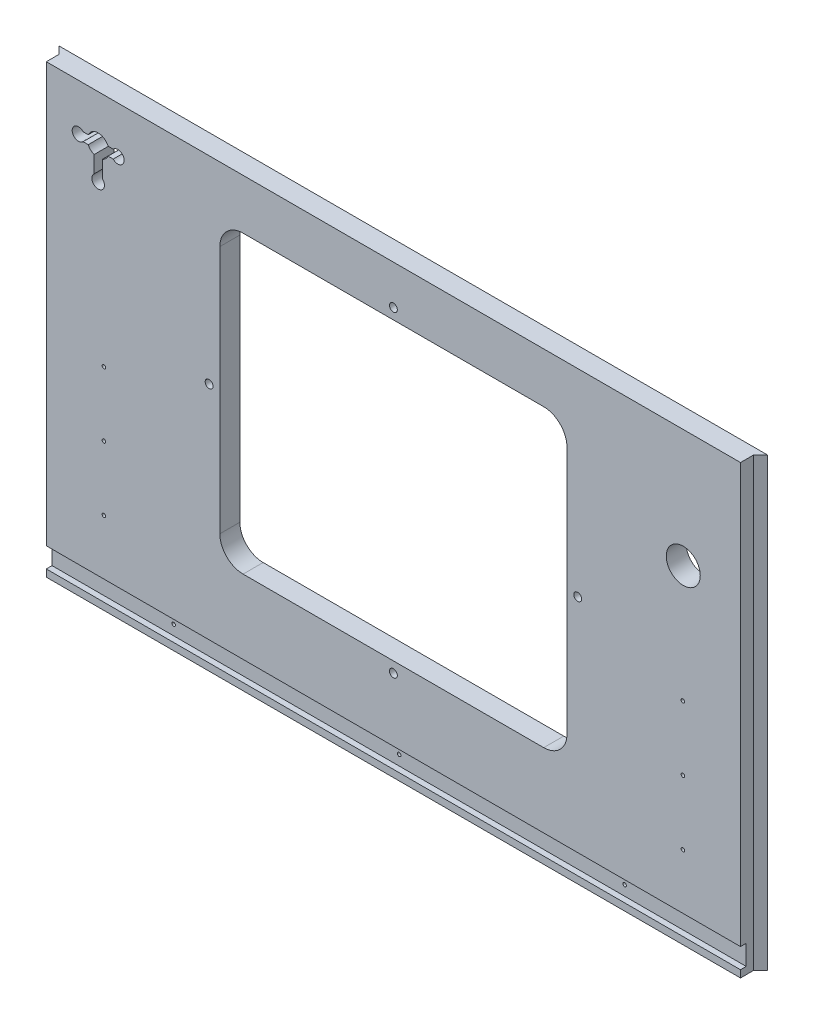
SolidWorks part; units mm, degrees
material "Maple"
ref_plane "Front Plane" through (0, 0, 0) normal (0, 0, 1) x (1, 0, 0)
ref_plane "Top Plane" through (0, 0, 0) normal (0, 1, 0) x (1, 0, 0)
ref_plane "Right Plane" through (0, 0, 0) normal (1, 0, 0) x (0, 0, -1)
sketch "Sketch1" plane through (0, 0, 0) normal (0, 0, 1) x (1, 0, 0)
  line L0 (8932.6508, -5243.5125) -> (10226.1458, -5243.5125)
  line L1 (9086.3208, -4722.0918) -> (10222.9708, -4853.7812)
  line L2 (8914.8708, -6342.0625) -> (10197.5708, -6342.0625)
  line L3 (8914.8708, -5808.6625) -> (10197.5708, -5808.6625)
  line L4 (8919.6333, -5253.0375) -> (10218.2083, -5253.0375)
  line L5 (9134.2633, -4656.1375) -> (9134.2633, -4638.3575)
  line L6 (9091.0833, -4638.3575) -> (9134.2633, -4638.3575)
  line L7 (9091.0833, -4567.2375) -> (9091.0833, -4638.3575)
  line L8 (9134.2633, -4656.1375) -> (9581.3033, -4656.1375)
  line L9 (9091.0833, -4567.2375) -> (9624.4833, -4567.2375)
  line L10 (9581.3033, -4656.1375) -> (9581.3033, -4638.3575)
  line L11 (9581.3033, -4638.3575) -> (9624.4833, -4638.3575)
  line L12 (9624.4833, -4567.2375) -> (9624.4833, -4638.3575)
  line L13 (8932.6508, -5225.7325) -> (9344.9775, -5225.7325)
  line L14 (8932.6508, -5256.2125) -> (8932.6508, -5243.5125)
  line L15 (8911.6958, -5256.2125) -> (8932.6508, -5256.2125)
  line L16 (8914.8708, -4722.0918) -> (9086.3208, -4722.0918)
  line L17 (8911.6958, -4715.5913) -> (8932.6508, -4715.5913)
  line L18 (8914.8708, -6342.0625) -> (8914.8708, -5808.6625)
  line L19 (12082.9917, -4722.0918) -> (10946.3417, -4853.7812)
  line L20 (12236.6617, -5243.5125) -> (10943.1667, -5243.5125)
  line L21 (10951.1042, -5253.0375) -> (12249.6792, -5253.0375)
  line L22 (10838.3917, -5656.2625) -> (11308.2917, -5656.2625)
  line L23 (10838.3917, -5719.7625) -> (11308.2917, -5719.7625)
  line L24 (10838.3917, -5742.5368) -> (11308.2917, -5742.5368)
  line L25 (10806.6417, -6342.0625) -> (11340.0417, -6342.0625)
  line L26 (10803.4667, -6335.7125) -> (11343.2167, -6335.7125)
  line L27 (10803.4667, -6317.9325) -> (11343.2167, -6317.9325)
  line L28 (10943.1667, -5225.7325) -> (11376.4483, -5225.7325)
  line L29 (11506.7292, -4754.5625) -> (10806.6417, -4827.5875)
  line L30 (11506.7292, -4567.2375) -> (11506.7292, -4754.5625)
  line L31 (10806.6417, -4567.2375) -> (10806.6417, -4827.5875)
  line L32 (10806.6417, -4567.2375) -> (11506.7292, -4567.2375)
  line L33 (10235.6708, -6329.3625) -> (10245.1958, -6329.3625)
  line L34 (10245.1958, -6329.3625) -> (10254.7208, -6278.5625)
  line L35 (10302.3458, -6329.3625) -> (10311.8708, -6278.5625)
  line L36 (10302.3458, -6329.3625) -> (10292.8208, -6329.3625)
  line L37 (10245.1958, -5821.3625) -> (10254.7208, -5872.1625)
  line L38 (10235.6708, -5821.3625) -> (10245.1958, -5821.3625)
  line L39 (10292.8208, -5821.3625) -> (10302.3458, -5821.3625)
  line L40 (10302.3458, -5821.3625) -> (10311.8708, -5872.1625)
  line L41 (10235.6708, -5821.3625) -> (10235.6708, -6329.3625)
  line L42 (10254.7208, -5872.1625) -> (10254.7208, -6278.5625)
  line L43 (10311.8708, -5872.1625) -> (10311.8708, -6278.5625)
  line L44 (10292.8208, -5821.3625) -> (10292.8208, -6329.3625)
  line L45 (8932.6508, -5225.7325) -> (8932.6508, -4715.5913)
  line L46 (8911.6958, -4715.5913) -> (8911.6958, -5256.2125)
  line L47 (8914.8708, -5248.275) -> (8914.8708, -4722.0918)
  line L48 (8919.6333, -5253.0375) -> (8914.8708, -5248.275)
  line L49 (8914.8708, -5145.0875) -> (8937.426, -5145.0875)
  line L50 (8914.8708, -5202.2375) -> (8937.426, -5202.2375)
  line L51 (10838.3917, -5656.2625) -> (10838.3917, -5719.7625)
  line L52 (10832.0417, -5736.1868) -> (10856.1717, -5736.1868)
  line L53 (10806.6417, -6342.0625) -> (10806.6417, -5818.7368)
  line L54 (10832.0417, -5649.9125) -> (10856.1717, -5649.9125)
  line L55 (10832.0417, -5726.1125) -> (10856.1717, -5726.1125)
  line L56 (10806.6417, -5818.7368) -> (10833.9015, -5818.7368)
  line L57 (10832.0417, -5806.0442) -> (10851.6815, -5806.0442)
  line L58 (10856.1717, -5801.5541) -> (10856.1717, -5736.1868)
  line L59 (10838.3917, -5814.2467) -> (10838.3917, -5742.5368)
  line L60 (10832.0417, -5806.0442) -> (10832.0417, -5736.1868)
  line L61 (10803.4667, -6317.9325) -> (10803.4667, -6335.7125)
  line L62 (10197.5708, -5808.6625) -> (10197.5708, -6342.0625)
  line L63 (9762.3842, -6348.4125) -> (9762.3842, -5802.3125)
  line L64 (9780.1642, -6348.4125) -> (9762.3842, -6348.4125)
  line L65 (9780.1642, -5802.3125) -> (9780.1642, -6348.4125)
  line L66 (9762.3842, -5802.3125) -> (9780.1642, -5802.3125)
  line L67 (9332.2775, -6348.4125) -> (9332.2775, -5802.3125)
  line L68 (9332.2775, -6348.4125) -> (9350.0575, -6348.4125)
  line L69 (9350.0575, -5802.3125) -> (9350.0575, -6348.4125)
  line L70 (9332.2775, -5802.3125) -> (9350.0575, -5802.3125)
  line L71 (9993.8374, -6061.075) -> (9993.8374, -6045.2418)
  line L72 (9998.5999, -6065.8375) -> (10014.4331, -6065.8375)
  line L73 (9998.5999, -6084.8875) -> (10014.4331, -6084.8875)
  line L74 (9993.8374, -6105.4832) -> (9993.8374, -6089.65)
  line L75 (9974.7874, -6105.4832) -> (9974.7874, -6089.65)
  line L76 (9954.1917, -6084.8875) -> (9970.0249, -6084.8875)
  line L77 (9974.7874, -6061.075) -> (9974.7874, -6045.2418)
  line L78 (9954.1917, -6065.8375) -> (9970.0249, -6065.8375)
  line L79 (10793.9417, -6237.2875) -> (10816.4969, -6237.2875)
  line L80 (10793.9417, -6294.4375) -> (10816.4969, -6294.4375)
  line L81 (10856.1717, -5649.9125) -> (10856.1717, -5726.1125)
  line L82 (10832.0417, -5726.1125) -> (10832.0417, -5649.9125)
  line L83 (10226.1458, -5225.7325) -> (10226.1458, -5243.5125)
  line L84 (10205.1908, -5257.8) -> (10205.1908, -4844.2499)
  line L85 (10230.9083, -4844.2499) -> (10230.9083, -5257.8)
  line L86 (10205.1908, -5257.8) -> (10230.9083, -5257.8)
  line L87 (10205.1908, -4844.2499) -> (10230.9083, -4844.2499)
  line L88 (10946.3417, -5176.8375) -> (10968.8969, -5176.8375)
  line L89 (9349.4676, -5141.9125) -> (9358.2674, -5141.9125)
  line L90 (10946.3417, -5119.6875) -> (10968.8969, -5119.6875)
  line L91 (9929.011, -4660.9635) -> (10066.0807, -4660.9635)
  line L92 (9929.011, -4678.7435) -> (10066.0807, -4678.7435)
  line L93 (10943.1667, -5225.7325) -> (10943.1667, -5243.5125)
  line L94 (10946.3417, -5248.275) -> (10951.1042, -5253.0375)
  line L95 (10946.3417, -5257.8063) -> (10946.3417, -4849.0188)
  line L96 (10964.1217, -5257.8) -> (10964.1217, -4844.2499)
  line L97 (10938.4042, -4844.2499) -> (10938.4042, -5257.8)
  line L98 (10938.4042, -5257.8) -> (10964.1217, -5257.8)
  line L99 (10964.1217, -4844.2499) -> (10938.4042, -4844.2499)
  line L100 (10344.8908, -4560.8875) -> (10369.0208, -4560.8875)
  line L101 (10344.8908, -4560.8875) -> (10369.0208, -4560.8875)
  line L102 (10800.2917, -4560.8875) -> (10824.4217, -4560.8875)
  line L103 (10200.4156, -5119.6875) -> (10222.9708, -5119.6875)
  line L104 (10200.4156, -5176.8375) -> (10222.9708, -5176.8375)
  line L105 (9344.9775, -5146.4026) -> (9344.9775, -5225.7325)
  line L106 (10344.8908, -4560.8875) -> (10344.8908, -4833.9375)
  line L107 (9792.8642, -5225.7325) -> (9792.8642, -5146.4026)
  line L108 (9362.7575, -5225.7325) -> (9775.0842, -5225.7325)
  line L109 (9680.3633, -4761.8396) -> (9680.3633, -4559.9604)
  line L110 (9656.2333, -4559.9604) -> (9680.3633, -4559.9604)
  line L111 (9656.2333, -4761.8396) -> (9680.3633, -4761.8396)
  line L112 (9656.2333, -4761.8396) -> (9656.2333, -4559.9604)
  line L113 (9779.5743, -5141.9125) -> (9788.374, -5141.9125)
  line L114 (10070.5708, -4665.4536) -> (10070.5708, -4674.2534)
  line L115 (9924.5208, -4674.2534) -> (9924.5208, -4665.4536)
  line L116 (12127.4417, -6188.3925) -> (12205.5015, -6188.3925)
  line L117 (12209.9917, -6170.6125) -> (12209.9917, -6183.9024)
  line L118 (9792.8642, -5225.7325) -> (10226.1458, -5225.7325)
  line L119 (9662.5833, -4754.5625) -> (10362.6708, -4827.5875)
  line L120 (9662.5833, -4567.2375) -> (9662.5833, -4754.5625)
  line L121 (10362.6708, -4567.2375) -> (10362.6708, -4827.5875)
  line L122 (9662.5833, -4567.2375) -> (10362.6708, -4567.2375)
  line L123 (10824.4217, -4833.9375) -> (10800.2917, -4833.9375)
  line L124 (10800.2917, -4833.9375) -> (10800.2917, -4560.8875)
  line L125 (10824.4217, -4560.8875) -> (10824.4217, -4833.9375)
  line L126 (10344.8908, -4833.9375) -> (10369.0208, -4833.9375)
  line L127 (10369.0208, -4833.9375) -> (10369.0208, -4560.8875)
  line L128 (10222.9708, -5248.275) -> (10218.2083, -5253.0375)
  line L129 (10222.9708, -5257.8063) -> (10222.9708, -4849.0188)
  line L130 (11734.6544, -5701.375) -> (11739.2301, -5701.375)
  line L131 (9362.7575, -5225.7325) -> (9362.7575, -5146.4026)
  line L132 (9775.0842, -5146.4026) -> (9775.0842, -5225.7325)
  line L133 (11761.3864, -5701.375) -> (11756.8282, -5701.375)
  line L134 (11734.6544, -5693.755) -> (11739.2301, -5693.755)
  line L135 (11761.4039, -5693.755) -> (11756.8282, -5693.755)
  line L136 (11734.6544, -5701.375) -> (11739.2301, -5701.375)
  line L137 (11744.3462, -5721.3024) -> (11744.3462, -5706.4179)
  line L138 (11751.7122, -5721.3024) -> (11751.7122, -5706.4179)
  line L139 (11740.0917, -6170.6125) -> (11740.0917, -6183.9024)
  line L140 (11689.2917, -6188.3925) -> (11822.6417, -6188.3925)
  line L141 (11689.2917, -6348.4093) -> (11689.2917, -6164.2657)
  line L142 (11689.2917, -6164.2657) -> (11746.4417, -6164.2657)
  line L143 (11746.4417, -6164.2657) -> (11746.4417, -6188.3925)
  line L144 (11689.2917, -6164.2657) -> (11746.4417, -6164.2657)
  line L145 (11340.0417, -5818.7368) -> (11340.0417, -6342.0625)
  line L146 (11290.5117, -5726.1125) -> (11314.6417, -5726.1125)
  line L147 (11290.5117, -5649.9125) -> (11290.5117, -5726.1125)
  line L148 (11340.0417, -5818.7368) -> (11312.7818, -5818.7368)
  line L149 (11314.6417, -5806.0442) -> (11295.0018, -5806.0442)
  line L150 (11290.5117, -5801.5541) -> (11290.5117, -5736.1868)
  line L151 (11308.2917, -5814.2467) -> (11308.2917, -5742.5368)
  line L152 (11314.6417, -5806.0442) -> (11314.6417, -5736.1868)
  line L153 (11290.5117, -5736.1868) -> (11314.6417, -5736.1868)
  line L154 (11848.0417, -6267.1325) -> (11962.3417, -6267.1325)
  line L155 (11962.3417, -6267.1325) -> (11962.3417, -6203.6325)
  line L156 (11343.2167, -6317.9325) -> (11343.2167, -6335.7125)
  line L157 (11365.4417, -5656.2625) -> (11365.4417, -5719.7625)
  line L158 (11365.4417, -5656.2625) -> (11479.7417, -5656.2625)
  line L159 (11778.1917, -6071.3937) -> (11802.3217, -6071.3937)
  line L160 (11314.6417, -5726.1125) -> (11314.6417, -5649.9125)
  line L161 (11314.6417, -5649.9125) -> (11290.5117, -5649.9125)
  line L162 (11308.2917, -5719.7625) -> (11308.2917, -5656.2625)
  line L163 (11689.2917, -6348.4093) -> (11713.4217, -6348.4093)
  line L164 (12203.6417, -6164.2657) -> (12260.7917, -6164.2657)
  line L165 (11713.4217, -6348.4093) -> (11713.4217, -6164.2657)
  line L166 (11695.6417, -6342.0625) -> (11695.6417, -6170.6125)
  line L167 (11695.6417, -6048.5337) -> (11699.4517, -6052.3437)
  line L168 (11822.6417, -6292.5325) -> (11822.6417, -6188.3925)
  line L169 (11695.6417, -6342.0625) -> (11695.6417, -6170.6125)
  line L170 (11848.0417, -6203.6325) -> (11962.3417, -6203.6325)
  line L171 (11848.0417, -6203.6325) -> (11848.0417, -6267.1325)
  line L172 (11987.7417, -6267.1325) -> (11987.7417, -6203.6325)
  line L173 (11784.5417, -6077.7437) -> (11784.5417, -6141.2438)
  line L174 (11517.8417, -5656.2625) -> (11632.1417, -5656.2625)
  line L175 (11632.1417, -5656.2625) -> (11632.1417, -5719.7625)
  line L176 (11632.1417, -5719.7625) -> (11517.8417, -5719.7625)
  line L177 (11517.8417, -5719.7625) -> (11517.8417, -5656.2625)
  line L178 (11692.4667, -6028.2137) -> (11692.4667, -6045.9937)
  line L179 (11695.6417, -5979.3188) -> (11718.1969, -5979.3188)
  line L180 (11695.6417, -5922.1687) -> (11718.1969, -5922.1687)
  line L181 (11821.0415, -5722.9375) -> (11821.0415, -5943.6)
  line L182 (11687.7042, -5651.5) -> (11701.9917, -5651.5)
  line L183 (11687.7042, -5651.5) -> (11687.7042, -6055.5251)
  line L184 (11687.7042, -6055.5251) -> (11701.9917, -6055.5251)
  line L185 (11701.9917, -6055.5251) -> (11701.9917, -5651.5)
  line L186 (11695.6417, -6055.2013) -> (11695.6417, -5649.595)
  line L187 (11695.6417, -5656.2625) -> (11695.6417, -6048.5337)
  line L188 (11695.6417, -6170.6125) -> (11740.0917, -6170.6125)
  line L189 (12203.6417, -6164.2657) -> (12203.6417, -6188.3925)
  line L190 (12254.4417, -6342.0625) -> (12254.4417, -6170.6125)
  line L191 (12129.0419, -5943.6) -> (12129.0419, -5722.9375)
  line L192 (12254.4417, -6048.5337) -> (12250.6317, -6052.3437)
  line L193 (12257.6167, -6045.9937) -> (12257.6167, -6028.2137)
  line L194 (12248.0917, -5651.5) -> (12262.3792, -5651.5)
  line L195 (12262.3792, -5651.5) -> (12262.3792, -6055.5251)
  line L196 (12262.3792, -6055.5251) -> (12248.0917, -6055.5251)
  line L197 (12248.0917, -6055.5251) -> (12248.0917, -5651.5)
  line L198 (12254.4417, -6141.2438) -> (12254.4417, -6077.7437)
  line L199 (12236.6617, -6164.2657) -> (12260.7917, -6164.2657)
  line L200 (12102.0417, -6267.1325) -> (11987.7417, -6267.1325)
  line L201 (11330.1865, -6237.2875) -> (11352.7417, -6237.2875)
  line L202 (11330.1865, -6294.4375) -> (11352.7417, -6294.4375)
  line L203 (11474.6617, -5851.8425) -> (11492.4417, -5851.8425)
  line L204 (11474.6617, -5808.6625) -> (11474.6617, -5851.8425)
  line L205 (11403.5417, -5808.6625) -> (11474.6617, -5808.6625)
  line L206 (11492.4417, -5851.8425) -> (11492.4417, -6298.8825)
  line L207 (11403.5417, -6342.0625) -> (11403.5417, -5808.6625)
  line L208 (11474.6617, -6298.8825) -> (11492.4417, -6298.8825)
  line L209 (11474.6617, -6342.0625) -> (11474.6617, -6298.8825)
  line L210 (11403.5417, -6342.0625) -> (11474.6617, -6342.0625)
  line L211 (11619.4417, -5851.8425) -> (11601.6617, -5851.8425)
  line L212 (11601.6617, -5808.6625) -> (11601.6617, -5851.8425)
  line L213 (11530.5417, -5808.6625) -> (11601.6617, -5808.6625)
  line L214 (11619.4417, -5851.8425) -> (11619.4417, -6298.8825)
  line L215 (11530.5417, -6342.0625) -> (11530.5417, -5808.6625)
  line L216 (11619.4417, -6298.8825) -> (11601.6617, -6298.8825)
  line L217 (11601.6617, -6342.0625) -> (11601.6617, -6298.8825)
  line L218 (11530.5417, -6342.0625) -> (11601.6617, -6342.0625)
  line L219 (11479.7417, -5719.7625) -> (11479.7417, -5656.2625)
  line L220 (11365.4417, -5719.7625) -> (11479.7417, -5719.7625)
  line L221 (11778.1917, -6147.5937) -> (11802.3217, -6147.5937)
  line L222 (11802.3217, -6071.3937) -> (11802.3217, -6147.5937)
  line L223 (11778.1917, -6147.5937) -> (11778.1917, -6071.3937)
  line L224 (12254.4417, -5922.1687) -> (12231.8865, -5922.1687)
  line L225 (12254.4417, -5979.3188) -> (12231.8865, -5979.3188)
  line L226 (12254.4417, -6055.2013) -> (12254.4417, -5649.595)
  line L227 (12254.4417, -6048.5337) -> (12254.4417, -5656.2625)
  line L228 (11841.6917, -5702.2873) -> (12108.3917, -5702.2873)
  line L229 (11822.6417, -6292.5325) -> (12127.4417, -6292.5325)
  line L230 (12127.4417, -6292.5325) -> (12127.4417, -6188.3925)
  line L231 (12254.4417, -6170.6125) -> (12209.9917, -6170.6125)
  line L232 (11695.6417, -6342.0625) -> (12254.4417, -6342.0625)
  line L233 (12236.6617, -6348.4093) -> (12260.7917, -6348.4093)
  line L234 (12260.7917, -6348.4093) -> (12260.7917, -6164.2657)
  line L235 (12236.6617, -6348.4093) -> (12236.6617, -6164.2657)
  line L236 (12102.0417, -6203.6325) -> (12102.0417, -6267.1325)
  line L237 (11987.7417, -6203.6325) -> (12102.0417, -6203.6325)
  line L238 (12236.6617, -6147.5937) -> (12236.6617, -6071.3937)
  line L239 (12203.6417, -6188.3925) -> (12260.7917, -6188.3925)
  line L240 (11098.7417, -4665.4536) -> (11098.7417, -4674.2534)
  line L241 (11394.2283, -5146.4026) -> (11394.2283, -5225.7325)
  line L242 (11376.4483, -5225.7325) -> (11376.4483, -5146.4026)
  line L243 (11394.2283, -5225.7325) -> (11806.555, -5225.7325)
  line L244 (11841.6917, -5964.2502) -> (12108.3917, -5964.2502)
  line L245 (12236.6617, -6147.5937) -> (12260.7917, -6147.5937)
  line L246 (12236.6617, -5256.2125) -> (12236.6617, -5243.5125)
  line L247 (12260.7917, -6147.5937) -> (12260.7917, -6071.3937)
  line L248 (12260.7917, -6071.3937) -> (12236.6617, -6071.3937)
  line L249 (12254.4417, -6077.7437) -> (11784.5417, -6077.7437)
  line L250 (11784.5417, -6141.2438) -> (12254.4417, -6141.2438)
  line L252 (12254.4417, -5656.2625) -> (11695.6417, -5656.2625)
  line L253 (11699.4517, -6052.3437) -> (12250.6317, -6052.3437)
  line L254 (11692.4667, -6045.9937) -> (12257.6167, -6045.9937)
  line L255 (11692.4667, -6028.2137) -> (12257.6167, -6028.2137)
  line L256 (11824.335, -5146.4026) -> (11824.335, -5225.7325)
  line L257 (11811.0451, -5141.9125) -> (11819.8449, -5141.9125)
  line L258 (11244.7917, -4674.2534) -> (11244.7917, -4665.4536)
  line L259 (11806.555, -5225.7325) -> (11806.555, -5146.4026)
  line L260 (11488.9492, -4761.8396) -> (11488.9492, -4559.9604)
  line L261 (11488.9492, -4559.9604) -> (11513.0792, -4559.9604)
  line L262 (11488.9492, -4761.8396) -> (11513.0792, -4761.8396)
  line L263 (11513.0792, -4761.8396) -> (11513.0792, -4559.9604)
  line L264 (11240.3015, -4660.9635) -> (11103.2318, -4660.9635)
  line L265 (11103.2318, -4678.7435) -> (11240.3015, -4678.7435)
  line L266 (12236.6617, -5225.7325) -> (12236.6617, -4715.5913)
  line L267 (12257.6167, -4715.5913) -> (12257.6167, -5256.2125)
  line L268 (12254.4417, -5248.275) -> (12254.4417, -4722.0918)
  line L269 (12236.6617, -5225.7325) -> (11824.335, -5225.7325)
  line L270 (12035.0492, -4656.1375) -> (12035.0492, -4638.3575)
  line L271 (12078.2292, -4638.3575) -> (12035.0492, -4638.3575)
  line L272 (12078.2292, -4567.2375) -> (12078.2292, -4638.3575)
  line L273 (12035.0492, -4656.1375) -> (11588.0092, -4656.1375)
  line L274 (11544.8292, -4567.2375) -> (12078.2292, -4567.2375)
  line L275 (11588.0092, -4656.1375) -> (11588.0092, -4638.3575)
  line L276 (11544.8292, -4638.3575) -> (11588.0092, -4638.3575)
  line L277 (11544.8292, -4567.2375) -> (11544.8292, -4638.3575)
  line L278 (12249.6792, -5253.0375) -> (12254.4417, -5248.275)
  line L280 (12257.6167, -5256.2125) -> (12236.6617, -5256.2125)
  line L281 (12231.8865, -5145.0875) -> (12254.4417, -5145.0875)
  line L282 (12231.8865, -5202.2375) -> (12254.4417, -5202.2375)
  line L283 (12236.6617, -4715.5913) -> (12257.6167, -4715.5913)
  line L284 (12082.9917, -4722.0918) -> (12254.4417, -4722.0918)
  line L285 (11380.9385, -5141.9125) -> (11389.7382, -5141.9125)
  circle A0 centre (8923.7608, -4778.9042) radius 1.5875
  circle A1 centre (9062.6598, -4736.3765) radius 2.3685
  circle A2 centre (9051.3958, -6281.7375) radius 22.225
  circle A3 centre (9083.1458, -6249.9875) radius 1.5875
  circle A4 centre (9083.1458, -6313.4875) radius 1.5875
  circle A5 centre (9019.6458, -6249.9875) radius 1.5875
  circle A6 centre (9019.6458, -6313.4875) radius 1.5875
  circle A7 centre (8972.3383, -5202.2375) radius 1.5875
  circle A8 centre (8923.7608, -5015.9708) radius 1.5875
  circle A9 centre (8923.7608, -5134.5042) radius 1.5875
  circle A10 centre (9054.5708, -5234.6225) radius 1.5875
  circle A11 centre (8923.7608, -4897.4375) radius 1.5875
  circle A12 centre (8972.3383, -5087.9375) radius 1.5875
  circle A13 centre (8972.3383, -5145.0875) radius 1.5875
  circle A14 centre (10847.2817, -5668.9625) radius 1.5875
  circle A15 centre (10847.2817, -5707.0625) radius 1.5875
  circle A16 centre (10847.2817, -5755.2368) radius 1.5875
  circle A17 centre (10851.4092, -6237.2875) radius 1.5875
  circle A18 centre (10851.4092, -6294.4375) radius 1.5875
  circle A19 centre (10847.2817, -5793.3442) radius 1.5875
  arc A20 (10833.9015, -5818.7368) -> (10838.3917, -5814.2467) centre (10836.1466, -5816.4918) ccw
  arc A21 (10851.6815, -5806.0442) -> (10856.1717, -5801.5541) centre (10853.9266, -5803.7992) ccw
  circle A22 centre (10882.8417, -6040.4375) radius 1.5875
  circle A23 centre (10882.8417, -6218.2375) radius 1.5875
  circle A24 centre (10882.8417, -5862.6375) radius 1.5875
  circle A25 centre (10908.2417, -6326.8225) radius 1.5875
  circle A26 centre (10908.2417, -6326.8225) radius 1.5875
  circle A27 centre (10851.4092, -6180.1375) radius 1.5875
  circle A28 centre (10815.5317, -4783.4231) radius 1.5875
  circle A29 centre (10815.5317, -4696.9488) radius 1.5875
  circle A30 centre (10815.5317, -4610.4746) radius 1.5875
  circle A31 centre (10979.1323, -4867.0082) radius 2.3685
  circle A32 centre (10190.1802, -4867.0082) radius 2.3685
  circle A33 centre (10955.2317, -4929.9812) radius 1.5875
  circle A34 centre (10955.2317, -5031.5812) radius 1.5875
  circle A35 centre (10214.0808, -4929.9812) radius 1.5875
  circle A36 centre (10214.0808, -5031.5812) radius 1.5875
  circle A37 centre (9341.1675, -6265.8625) radius 1.5875
  circle A38 centre (9771.2742, -5884.8625) radius 1.5875
  circle A39 centre (9771.2742, -6138.8625) radius 1.5875
  circle A40 centre (9771.2742, -6011.8625) radius 1.5875
  arc A41 (10036.2287, -6113.8083) -> (10051.3426, -6111.6033) centre (10042.9639, -6107.0732) ccw
  arc A42 (10051.3426, -6111.6033) -> (10051.3426, -6039.1217) centre (9984.3124, -6075.3625) ccw
  arc A43 (10051.3426, -6039.1217) -> (10036.2287, -6036.9167) centre (10042.9639, -6043.6518) ccw
  arc A44 (10034.5851, -6102.5431) -> (10034.5851, -6048.1819) centre (9984.3124, -6075.3625) ccw
  arc A45 (10034.5851, -6102.5431) -> (10036.2287, -6113.8083) centre (10042.9639, -6107.0732) ccw
  arc A46 (10036.2287, -6036.9167) -> (10034.5851, -6048.1819) centre (10042.9639, -6043.6518) ccw
  arc A47 (9945.8666, -6127.2787) -> (9948.0717, -6142.3927) centre (9952.6018, -6134.0139) ccw
  arc A48 (9948.0717, -6142.3927) -> (10020.5532, -6142.3927) centre (9984.3124, -6075.3625) ccw
  arc A49 (10020.5532, -6142.3927) -> (10022.7583, -6127.2787) centre (10016.0231, -6134.0139) ccw
  arc A50 (9957.1319, -6125.6352) -> (10011.493, -6125.6352) centre (9984.3124, -6075.3625) ccw
  arc A51 (9957.1319, -6125.6352) -> (9945.8666, -6127.2787) centre (9952.6018, -6134.0139) ccw
  arc A52 (10022.7583, -6127.2787) -> (10011.493, -6125.6352) centre (10016.0231, -6134.0139) ccw
  arc A53 (9932.3962, -6036.9167) -> (9917.2822, -6039.1217) centre (9925.661, -6043.6518) ccw
  arc A54 (9917.2822, -6039.1217) -> (9917.2822, -6111.6033) centre (9984.3124, -6075.3625) ccw
  arc A55 (9917.2822, -6111.6033) -> (9932.3962, -6113.8083) centre (9925.661, -6107.0732) ccw
  arc A56 (9934.0398, -6048.1819) -> (9934.0398, -6102.5431) centre (9984.3124, -6075.3625) ccw
  arc A57 (9934.0398, -6048.1819) -> (9932.3962, -6036.9167) centre (9925.661, -6043.6518) ccw
  arc A58 (9932.3962, -6113.8083) -> (9934.0398, -6102.5431) centre (9925.661, -6107.0732) ccw
  arc A59 (9945.8666, -6023.4463) -> (9957.1319, -6025.0898) centre (9952.6018, -6016.7111) ccw
  arc A60 (10011.493, -6025.0898) -> (10022.7583, -6023.4463) centre (10016.0231, -6016.7111) ccw
  arc A61 (10011.493, -6025.0898) -> (9957.1319, -6025.0898) centre (9984.3124, -6075.3625) ccw
  arc A62 (9948.0717, -6008.3323) -> (9945.8666, -6023.4463) centre (9952.6018, -6016.7111) ccw
  arc A63 (10020.5532, -6008.3323) -> (9948.0717, -6008.3323) centre (9984.3124, -6075.3625) ccw
  arc A64 (10022.7583, -6023.4463) -> (10020.5532, -6008.3323) centre (10016.0231, -6016.7111) ccw
  arc A65 (10005.0943, -6187.7574) -> (10096.7073, -6096.1443) centre (9984.3124, -6075.3625) ccw
  arc A66 (9993.8374, -6178.3911) -> (10005.0943, -6187.7574) centre (10003.3624, -6178.3911) ccw
  arc A67 (10001.6306, -6169.0249) -> (10077.9748, -6092.6807) centre (9984.3124, -6075.3625) ccw
  arc A68 (10087.3411, -6084.8875) -> (10077.9748, -6092.6807) centre (10087.3411, -6094.4125) ccw
  arc A69 (10001.6306, -6169.0249) -> (9993.8374, -6178.3911) centre (10003.3624, -6178.3911) ccw
  arc A70 (9963.5306, -6187.7574) -> (9974.7874, -6178.3911) centre (9965.2624, -6178.3911) ccw
  arc A71 (9871.9176, -6096.1443) -> (9963.5306, -6187.7574) centre (9984.3124, -6075.3625) ccw
  arc A72 (9881.2838, -6084.8875) -> (9871.9176, -6096.1443) centre (9881.2838, -6094.4125) ccw
  arc A73 (9890.65, -6092.6807) -> (9966.9943, -6169.0249) centre (9984.3124, -6075.3625) ccw
  arc A74 (9974.7874, -6178.3911) -> (9966.9943, -6169.0249) centre (9965.2624, -6178.3911) ccw
  arc A75 (9890.65, -6092.6807) -> (9881.2838, -6084.8875) centre (9881.2838, -6094.4125) ccw
  arc A76 (9871.9176, -6054.5807) -> (9881.2838, -6065.8375) centre (9881.2838, -6056.3125) ccw
  arc A77 (9963.5306, -5962.9676) -> (9871.9176, -6054.5807) centre (9984.3124, -6075.3625) ccw
  arc A78 (9974.7874, -5972.3339) -> (9963.5306, -5962.9676) centre (9965.2624, -5972.3339) ccw
  arc A79 (9966.9943, -5981.7001) -> (9890.65, -6058.0443) centre (9984.3124, -6075.3625) ccw
  arc A80 (9881.2838, -6065.8375) -> (9890.65, -6058.0443) centre (9881.2838, -6056.3125) ccw
  arc A81 (9966.9943, -5981.7001) -> (9974.7874, -5972.3339) centre (9965.2624, -5972.3339) ccw
  arc A82 (10077.9748, -6058.0443) -> (10087.3411, -6065.8375) centre (10087.3411, -6056.3125) ccw
  arc A83 (9993.8374, -5972.3339) -> (10001.6306, -5981.7001) centre (10003.3624, -5972.3339) ccw
  arc A84 (10077.9748, -6058.0443) -> (10001.6306, -5981.7001) centre (9984.3124, -6075.3625) ccw
  arc A85 (10087.3411, -6065.8375) -> (10096.7073, -6054.5807) centre (10087.3411, -6056.3125) ccw
  arc A86 (10096.7073, -6054.5807) -> (10005.0943, -5962.9676) centre (9984.3124, -6075.3625) ccw
  arc A87 (10005.0943, -5962.9676) -> (9993.8374, -5972.3339) centre (10003.3624, -5972.3339) ccw
  arc A88 (10014.4331, -6065.8375) -> (10018.7361, -6059.0339) centre (10014.4331, -6061.075) ccw
  arc A89 (10018.7361, -6059.0339) -> (10000.641, -6040.9388) centre (9984.3124, -6075.3625) ccw
  arc A90 (10000.641, -6040.9388) -> (9993.8374, -6045.2418) centre (9998.5999, -6045.2418) ccw
  arc A91 (9993.8374, -6061.075) -> (9998.5999, -6065.8375) centre (9998.5999, -6061.075) ccw
  arc A92 (9993.8374, -6105.4832) -> (10000.641, -6109.7862) centre (9998.5999, -6105.4832) ccw
  arc A93 (10000.641, -6109.7862) -> (10018.7361, -6091.6911) centre (9984.3124, -6075.3625) ccw
  arc A94 (10018.7361, -6091.6911) -> (10014.4331, -6084.8875) centre (10014.4331, -6089.65) ccw
  arc A95 (9998.5999, -6084.8875) -> (9993.8374, -6089.65) centre (9998.5999, -6089.65) ccw
  arc A96 (9954.1917, -6084.8875) -> (9949.8888, -6091.6911) centre (9954.1917, -6089.65) ccw
  arc A97 (9949.8888, -6091.6911) -> (9967.9839, -6109.7862) centre (9984.3124, -6075.3625) ccw
  arc A98 (9967.9839, -6109.7862) -> (9974.7874, -6105.4832) centre (9970.0249, -6105.4832) ccw
  arc A99 (9974.7874, -6089.65) -> (9970.0249, -6084.8875) centre (9970.0249, -6089.65) ccw
  arc A100 (9970.0249, -6065.8375) -> (9974.7874, -6061.075) centre (9970.0249, -6061.075) ccw
  arc A101 (9949.8888, -6059.0339) -> (9954.1917, -6065.8375) centre (9954.1917, -6061.075) ccw
  arc A102 (9967.9839, -6040.9388) -> (9949.8888, -6059.0339) centre (9984.3124, -6075.3625) ccw
  arc A103 (9974.7874, -6045.2418) -> (9967.9839, -6040.9388) centre (9970.0249, -6045.2418) ccw
  arc A104 (10096.7073, -6096.1443) -> (10087.3411, -6084.8875) centre (10087.3411, -6094.4125) ccw
  circle A105 centre (9771.2742, -6265.8625) radius 1.5875
  circle A106 centre (9341.1675, -5884.8625) radius 1.5875
  circle A107 centre (9341.1675, -6138.8625) radius 1.5875
  circle A108 centre (9341.1675, -6011.8625) radius 1.5875
  circle A109 centre (11037.2315, -4887.5494) radius 15.0812
  arc A110 (9349.4676, -5141.9125) -> (9344.9775, -5146.4026) centre (9347.2226, -5144.1576) ccw
  arc A111 (9362.7575, -5146.4026) -> (9358.2674, -5141.9125) centre (9360.5124, -5144.1576) ccw
  circle A112 centre (9946.7458, -4669.8535) radius 1.5875
  arc A113 (9924.5208, -4674.2534) -> (9929.011, -4678.7435) centre (9926.7659, -4676.4984) ccw
  circle A114 centre (11003.8092, -5176.8375) radius 1.5875
  circle A115 centre (11003.8092, -5119.6875) radius 1.5875
  circle A116 centre (10353.7808, -4696.9488) radius 1.5875
  circle A117 centre (10353.7808, -4610.4746) radius 1.5875
  circle A118 centre (10353.7808, -4783.4231) radius 1.5875
  circle A119 centre (11003.8092, -5062.5375) radius 1.5875
  circle A120 centre (9353.8675, -5160.9625) radius 1.5875
  circle A121 centre (9638.7708, -5234.6225) radius 1.5875
  circle A122 centre (9671.4733, -4724.1144) radius 1.5875
  circle A123 centre (9671.4733, -4661.3637) radius 1.5875
  circle A124 centre (9671.4733, -4598.6129) radius 1.5875
  arc A125 (9792.8642, -5146.4026) -> (9788.374, -5141.9125) centre (9790.6191, -5144.1576) ccw
  arc A126 (9779.5743, -5141.9125) -> (9775.0842, -5146.4026) centre (9777.3292, -5144.1576) ccw
  circle A127 centre (10048.3458, -4669.8535) radius 1.5875
  arc A128 (10070.5708, -4665.4536) -> (10066.0807, -4660.9635) centre (10068.3258, -4663.2086) ccw
  arc A129 (10066.0807, -4678.7435) -> (10070.5708, -4674.2534) centre (10068.3258, -4676.4984) ccw
  circle A130 centre (9997.5458, -4669.8535) radius 1.5875
  arc A131 (9929.011, -4660.9635) -> (9924.5208, -4665.4536) centre (9926.7659, -4663.2086) ccw
  circle A132 centre (10132.081, -4887.5494) radius 15.0812
  circle A133 centre (10165.5033, -5176.8375) radius 1.5875
  circle A134 centre (10165.5033, -5119.6875) radius 1.5875
  circle A135 centre (9486.3708, -5234.6225) radius 1.5875
  circle A136 centre (10165.5033, -5062.5375) radius 1.5875
  circle A137 centre (9206.9708, -5234.6225) radius 1.5875
  circle A138 centre (10070.5708, -5234.6225) radius 1.5875
  circle A139 centre (9918.1708, -5234.6225) radius 1.5875
  circle A140 centre (9783.9742, -5160.9625) radius 1.5875
  circle A141 centre (9783.9742, -5193.9825) radius 1.5875
  circle A142 centre (9353.8675, -5193.9825) radius 1.5875
  circle A143 centre (11073.3417, -6326.8225) radius 1.5875
  circle A144 centre (11073.3417, -6326.8225) radius 1.5875
  circle A145 centre (11295.2742, -6180.1375) radius 1.5875
  circle A146 centre (11295.2742, -6294.4375) radius 1.5875
  circle A147 centre (11295.2742, -6237.2875) radius 1.5875
  circle A148 centre (11975.0417, -5692.775) radius 3.4925
  circle A149 centre (11263.8417, -5862.6375) radius 1.5875
  arc A150 (11739.2301, -5701.375) -> (11744.3462, -5706.4179) centre (11748.0292, -5697.565) ccw
  arc A151 (11751.7122, -5706.4179) -> (11756.8282, -5701.375) centre (11748.0292, -5697.565) ccw
  arc A152 (11744.3462, -5721.3024) -> (11751.7122, -5721.3024) centre (11748.0292, -5725.505) ccw
  arc A153 (11734.6544, -5693.755) -> (11724.9787, -5697.565) centre (11730.5667, -5697.565) ccw
  arc A154 (11756.8282, -5693.755) -> (11739.2301, -5693.755) centre (11748.0292, -5697.565) ccw
  arc A155 (11724.9787, -5697.565) -> (11734.6544, -5701.375) centre (11730.5667, -5697.565) ccw
  arc A156 (11761.3864, -5701.375) -> (11771.0797, -5697.565) centre (11765.4842, -5697.565) ccw
  arc A157 (11771.0797, -5697.565) -> (11761.4039, -5693.755) centre (11765.4917, -5697.565) ccw
  arc A158 (11740.0917, -6183.9024) -> (11744.5818, -6188.3925) centre (11742.3367, -6186.1474) ccw
  arc A159 (12205.5015, -6188.3925) -> (12209.9917, -6183.9024) centre (12207.7466, -6186.1474) ccw
  circle A160 centre (11299.4017, -5793.3442) radius 1.5875
  arc A161 (11308.2917, -5814.2467) -> (11312.7818, -5818.7368) centre (11310.5367, -5816.4918) ccw
  arc A162 (11290.5117, -5801.5541) -> (11295.0018, -5806.0442) centre (11292.7567, -5803.7992) ccw
  circle A163 centre (11704.5317, -6314.149) radius 1.5875
  circle A164 centre (11748.9817, -6208.7125) radius 1.5875
  circle A165 centre (11263.8417, -6218.2375) radius 1.5875
  circle A166 centre (11263.8417, -6040.4375) radius 1.5875
  circle A167 centre (11238.4417, -6326.8225) radius 1.5875
  circle A168 centre (11238.4417, -6326.8225) radius 1.5875
  circle A169 centre (11299.4017, -5668.9625) radius 1.5875
  circle A170 centre (11299.4017, -5707.0625) radius 1.5875
  circle A171 centre (11726.7567, -6179.5025) radius 1.5875
  circle A172 centre (11704.5317, -6199.3198) radius 1.5875
  circle A173 centre (11748.9817, -6272.2125) radius 1.5875
  circle A174 centre (11704.5317, -6256.7344) radius 1.5875
  circle A175 centre (11299.4017, -5755.2368) radius 1.5875
  circle A176 centre (11913.4467, -6301.4225) radius 1.5875
  circle A177 centre (11790.2567, -6301.4225) radius 1.5875
  circle A178 centre (11793.4317, -6128.5437) radius 1.5875
  circle A179 centre (11753.1092, -5865.0188) radius 1.5875
  circle A180 centre (11809.9417, -6037.1038) radius 1.5875
  circle A181 centre (11809.9417, -6037.1038) radius 1.5875
  circle A182 centre (11753.1092, -5922.1687) radius 1.5875
  circle A183 centre (11975.0417, -5973.7625) radius 3.4925
  circle A184 centre (11975.0417, -6037.1038) radius 1.5875
  circle A185 centre (11753.1092, -5979.3188) radius 1.5875
  circle A186 centre (11975.0417, -6037.1038) radius 1.5875
  arc A187 (11841.6917, -5702.2873) -> (11821.0415, -5722.9375) centre (11841.6917, -5722.9375) ccw
  circle A188 centre (11811.5292, -5833.2687) radius 3.4925
  arc A189 (11821.0415, -5943.6) -> (11841.6917, -5964.2502) centre (11841.6917, -5943.6) ccw
  circle A190 centre (12196.9742, -5865.0188) radius 1.5875
  arc A191 (12129.0419, -5722.9375) -> (12108.3917, -5702.2873) centre (12108.3917, -5722.9375) ccw
  circle A192 centre (12036.6367, -6301.4225) radius 1.5875
  circle A193 centre (12159.8267, -6301.4225) radius 1.5875
  circle A194 centre (12138.5542, -5833.2687) radius 3.4925
  circle A195 centre (12197.2917, -5761.0375) radius 15.0812
  circle A196 centre (11793.4317, -6090.4437) radius 1.5875
  circle A197 centre (12196.9742, -5922.1687) radius 1.5875
  arc A198 (12108.3917, -5964.2502) -> (12129.0419, -5943.6) centre (12108.3917, -5943.6) ccw
  circle A199 centre (12196.9742, -5979.3188) radius 1.5875
  circle A200 centre (12201.1017, -6272.2125) radius 1.5875
  circle A201 centre (12245.5517, -6314.149) radius 1.5875
  circle A202 centre (12245.5517, -6256.7344) radius 1.5875
  circle A203 centre (12201.1017, -6208.7125) radius 1.5875
  circle A204 centre (12223.3267, -6179.5025) radius 1.5875
  circle A205 centre (12245.5517, -6199.3198) radius 1.5875
  circle A206 centre (11171.7667, -4669.8535) radius 1.5875
  circle A207 centre (11222.5667, -4669.8535) radius 1.5875
  arc A208 (11240.3015, -4678.7435) -> (11244.7917, -4674.2534) centre (11242.5466, -4676.4984) ccw
  circle A209 centre (11385.3383, -5193.9825) radius 1.5875
  circle A210 centre (12106.6527, -4736.3765) radius 2.3685
  circle A211 centre (12140.1417, -6037.1038) radius 1.5875
  circle A212 centre (12140.1417, -6037.1038) radius 1.5875
  circle A213 centre (12245.5517, -6090.4437) radius 1.5875
  circle A214 centre (12245.5517, -6128.5437) radius 1.5875
  circle A215 centre (11385.3383, -5160.9625) radius 1.5875
  arc A216 (11824.335, -5146.4026) -> (11819.8449, -5141.9125) centre (11822.0899, -5144.1576) ccw
  arc A217 (11811.0451, -5141.9125) -> (11806.555, -5146.4026) centre (11808.8001, -5144.1576) ccw
  circle A218 centre (11815.445, -5193.9825) radius 1.5875
  circle A219 centre (11815.445, -5160.9625) radius 1.5875
  circle A220 centre (11530.5417, -5234.6225) radius 1.5875
  circle A221 centre (11962.3417, -5234.6225) radius 1.5875
  arc A222 (11244.7917, -4665.4536) -> (11240.3015, -4660.9635) centre (11242.5466, -4663.2086) ccw
  circle A223 centre (11682.9417, -5234.6225) radius 1.5875
  circle A224 centre (11497.8392, -4724.1144) radius 1.5875
  circle A225 centre (11497.8392, -4661.3637) radius 1.5875
  circle A226 centre (11497.8392, -4598.6129) radius 1.5875
  circle A227 centre (11120.9667, -4669.8535) radius 1.5875
  arc A228 (11103.2318, -4660.9635) -> (11098.7417, -4665.4536) centre (11100.9867, -4663.2086) ccw
  arc A229 (11098.7417, -4674.2534) -> (11103.2318, -4678.7435) centre (11100.9867, -4676.4984) ccw
  circle A230 centre (12196.9742, -5202.2375) radius 1.5875
  circle A231 centre (12245.5517, -5015.9708) radius 1.5875
  circle A232 centre (12245.5517, -5134.5042) radius 1.5875
  circle A233 centre (12114.7417, -5234.6225) radius 1.5875
  circle A234 centre (12245.5517, -4897.4375) radius 1.5875
  circle A235 centre (12245.5517, -4778.9042) radius 1.5875
  circle A236 centre (12196.9742, -5087.9375) radius 1.5875
  circle A237 centre (12196.9742, -5145.0875) radius 1.5875
  circle A238 centre (11098.7417, -5234.6225) radius 1.5875
  circle A239 centre (11251.1417, -5234.6225) radius 1.5875
  arc A240 (11380.9385, -5141.9125) -> (11376.4483, -5146.4026) centre (11378.6934, -5144.1576) ccw
  arc A241 (11394.2283, -5146.4026) -> (11389.7382, -5141.9125) centre (11391.9833, -5144.1576) ccw
sketch "CabFrontOutline" plane through (0, 0, 0) normal (0, 0, 1) x (1, 0, 0)
  line L0 (11695.6417, -6055.2013) -> (11695.6417, -5649.595) construction
  line L1 (11695.6417, -6052.3437) -> (12324.2917, -6052.3437)
  line L3 (12324.2917, -6052.3437) -> (12324.2917, -5656.2625)
  line L4 (12324.2917, -5656.2625) -> (11695.6417, -5656.2625)
  line L5 (11695.6417, -5656.2625) -> (11695.6417, -6052.3437)
  point P1 (0, 0)
  point P2 (0, 0)
  dimension "CabFrontWidth" = 628.65
extrude "CabFront_Thickness" add sketch "CabFrontOutline" against normal blind 17.78
sketch "CabFront_CoinDoorCuts" plane through (0, 0, 0) normal (0, 0, 1) x (1, 0, 0)
  line L0 (11855.9665, -5700.6998) -> (12163.9669, -5700.6998)
  line L1 (12163.9669, -5700.6998) -> (12163.9669, -5962.6627)
  line L2 (12163.9669, -5962.6627) -> (11855.9665, -5962.6627)
  line L3 (11855.9665, -5962.6627) -> (11855.9665, -5700.6998)
  line L4 (11734.6544, -5693.755) -> (11739.2301, -5693.755)
  line L5 (11734.6544, -5701.375) -> (11739.2301, -5701.375)
  line L6 (11744.3462, -5706.4179) -> (11744.3462, -5721.3024)
  line L7 (11751.7122, -5706.4179) -> (11751.7122, -5721.3024)
  line L8 (11756.8282, -5701.375) -> (11761.3864, -5701.375)
  line L9 (11761.3864, -5693.755) -> (11756.8282, -5693.755)
  line L10 (11753.1092, -5865.0188) -> (11753.1092, -5922.1687) construction
  line L11 (11753.1092, -5922.1687) -> (11753.1092, -5979.3188) construction
  line L12 (11695.6417, -5656.2625) -> (11695.6417, -6052.3437) construction
  line L13 (12266.8242, -5865.0188) -> (12266.8242, -5922.1687) construction
  line L14 (12266.8242, -5922.1687) -> (12266.8242, -5979.3188) construction
  line L15 (12324.2917, -6052.3437) -> (12324.2917, -5656.2625) construction
  line L16 (11809.9417, -6037.1038) -> (12009.9667, -6037.1038) construction
  line L17 (12009.9667, -6037.1038) -> (12209.9917, -6037.1038) construction
  line L18 (12009.9667, -6037.1038) -> (12009.9667, -6052.3437) construction
  line L19 (11695.6417, -6052.3437) -> (12324.2917, -6052.3437) construction
  line L20 (12009.9667, -5691.1875) -> (12009.9667, -5700.6998) construction
  line L21 (11846.4542, -5831.6812) -> (11855.9665, -5831.6812) construction
  line L22 (12009.9667, -5972.175) -> (12009.9667, -5962.6627) construction
  line L23 (12173.4792, -5831.6812) -> (12163.9669, -5831.6812) construction
  line L24 (12009.9667, -5691.1875) -> (12009.9667, -5656.2625) construction
  line L25 (12324.2917, -5656.2625) -> (11695.6417, -5656.2625) construction
  arc A4 (11734.6544, -5693.755) -> (11734.6544, -5701.375) centre (11730.5667, -5697.565) ccw
  arc A5 (11724.9787, -5697.565) -> (11734.6544, -5701.375) centre (11730.5667, -5697.565) ccw construction
  arc A6 (11739.2301, -5693.755) -> (11756.8282, -5693.755) centre (11748.0292, -5697.565) cw
  arc A7 (11756.8282, -5693.755) -> (11739.2301, -5693.755) centre (11748.0292, -5697.565) ccw construction
  arc A8 (11744.3462, -5721.3024) -> (11751.7122, -5721.3024) centre (11748.0292, -5725.505) ccw
  arc A9 (11744.3462, -5721.3024) -> (11751.7122, -5721.3024) centre (11748.0292, -5725.505) ccw construction
  arc A10 (11739.2301, -5701.375) -> (11744.3462, -5706.4179) centre (11748.0292, -5697.565) ccw
  arc A11 (11739.2301, -5701.375) -> (11744.3462, -5706.4179) centre (11748.0292, -5697.565) ccw construction
  arc A12 (11751.7122, -5706.4179) -> (11756.8282, -5701.375) centre (11748.0292, -5697.565) ccw
  arc A13 (11751.7122, -5706.4179) -> (11756.8282, -5701.375) centre (11748.0292, -5697.565) ccw construction
  arc A14 (11761.3864, -5701.375) -> (11771.0797, -5697.565) centre (11765.4842, -5697.565) ccw
  arc A16 (11761.3864, -5701.375) -> (11771.0797, -5697.565) centre (11765.4842, -5697.565) ccw construction
  arc A17 (11771.0797, -5697.565) -> (11761.3864, -5693.755) centre (11765.4842, -5697.565) ccw
  circle A18 centre (12267.1417, -5761.0375) radius 15.0812
  circle A19 centre (12173.4792, -5831.6812) radius 3.4925
  circle A20 centre (12266.8242, -5865.0188) radius 1.5875
  circle A21 centre (12266.8242, -5922.1687) radius 1.5875
  circle A22 centre (12266.8242, -5979.3188) radius 1.5875
  circle A23 centre (12209.9917, -6037.1038) radius 1.5875
  circle A24 centre (12009.9667, -6037.1038) radius 1.5875
  circle A25 centre (11809.9417, -6037.1038) radius 1.5875
  circle A26 centre (11753.1092, -5979.3188) radius 1.5875
  circle A27 centre (11753.1092, -5922.1687) radius 1.5875
  circle A28 centre (11753.1092, -5865.0188) radius 1.5875
  circle A29 centre (11846.4542, -5831.6812) radius 3.4925
  circle A30 centre (12009.9667, -5972.175) radius 3.4925
  circle A31 centre (12009.9667, -5691.1875) radius 3.4925
  dimension "D1" = 57.4675
  dimension "D2" = 57.4675
  dimension "D3" = 57.15
  dimension "D4" = 34.925
  dimension "D5" = 308.0004
  dimension "D6" = 9.5123
  dimension "D7" = 261.9629
extrude "Cut-Extrude1" cut sketch "CabFront_CoinDoorCuts" against normal up to surface (17.78 mm away) up to face at (12009.9667, -5854.3031, -17.78)
sketch "CabFront_BottomLedge" plane through (0, 0, 0) normal (0, 0, 1) x (1, 0, 0)
  line L0 (11975.0417, -6028.2137) -> (11695.6417, -6028.2137)
  line L1 (11975.0417, -6028.2137) -> (11975.0417, -6052.3437) construction
  line L2 (11695.6417, -6055.2013) -> (11695.6417, -5649.595) construction
  line L3 (11692.4667, -6028.2137) -> (12257.6167, -6028.2137) construction
  line L4 (11699.4517, -6052.3437) -> (12250.6317, -6052.3437) construction
  line L5 (11695.6417, -6028.2137) -> (11695.6417, -6045.9937)
  line L6 (11695.6417, -6045.9937) -> (12324.2917, -6045.9937)
  line L7 (12324.2917, -6052.3437) -> (12324.2917, -5656.2625) construction
  line L9 (12324.2917, -6045.9937) -> (12324.2917, -6028.2137)
  line L10 (12324.2917, -6028.2137) -> (11975.0417, -6028.2137)
  dimension "D1" = 17.78
extrude "CabFrontBottomLedge_Depth" cut sketch "CabFront_BottomLedge" against normal blind 5.08
sketch "CabFront_EdgeBevel" plane through (0, -6052.3437, 0) normal (0, -1, 0) x (1, 0, 0)
  line L0 (11701.9917, -11.43) -> (11701.9917, 0)
  line L1 (11701.9917, 0) -> (11695.6417, 0)
  line L2 (11695.6417, 0) -> (11695.6417, -17.78)
  line L5 (12317.9417, -11.43) -> (12324.2917, -17.78)
  line L10 (11695.6417, -17.78) -> (11701.9917, -11.43)
  line L11 (12317.9417, -11.43) -> (12317.9417, 0)
  line L12 (11695.6417, 0) -> (12324.2917, 0) construction
  line L13 (12317.9417, 0) -> (12324.2917, 0)
  line L14 (12324.2917, 0) -> (12324.2917, -17.78)
  dimension "D1" = 6.35
  dimension "D2" = 6.35
  dimension "D3" = 6.35
  dimension "D4" = 6.35
extrude "Cut-Extrude4" cut sketch "CabFront_EdgeBevel" against normal up to surface (396.0813 mm away) up to face at (12009.9667, -5656.2625, -8.89)
fillet "Fillet1" radius 20.6502 4 edges at (11855.9665, -5700.6998, -8.89) (11855.9665, -5962.6627, -8.89) (12163.9669, -5962.6627, -8.89) (12163.9669, -5700.6998, -8.89)
